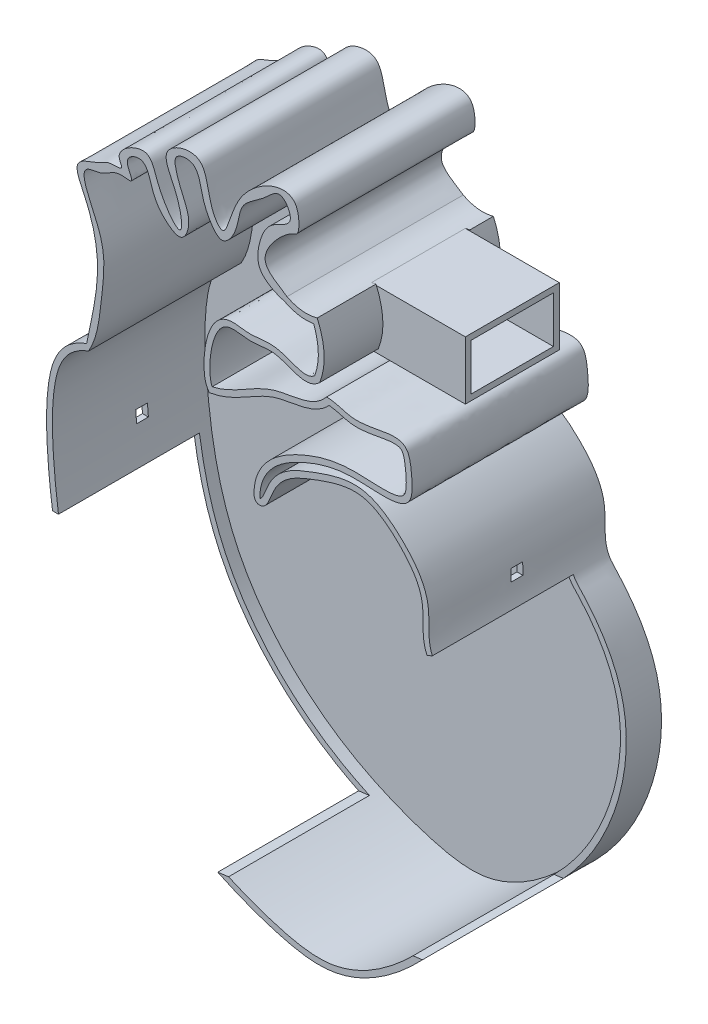
SolidWorks part; units mm, degrees
ref_plane "Front Plane" through (0, 0, 0) normal (0, 0, 1) x (1, 0, 0)
ref_plane "Top Plane" through (0, 0, 0) normal (0, 1, 0) x (1, 0, 0)
ref_plane "Right Plane" through (0, 0, 0) normal (1, 0, 0) x (0, 0, -1)
sketch "Sketch1" plane through (0, 0, 0) normal (0, 0, 1) x (1, 0, 0)
  line L0 (155.9186, 311.1659) -> (244.8186, 311.1659) construction
  line L1 (156.5316, 303.0783) -> (161.4308, 303.0783) construction
  line L2 (233.7391, 314.6833) -> (238.69, 317.0002) construction
  spline S0 degree 3 poles (163.9083, 338.1039) (161.9768, 337.4412) (157.1029, 334.2543) (154.9102, 324.3198) (155.5747, 306.9623) (159.3352, 282.8965) (178.2163, 259.8183) (198.5453, 249.6184) (218.658, 245.0232) (234.9705, 255.6289) (248.3574, 273.7717) (252.562, 297.43) (244.0287, 311.0697) (237.1441, 318.0888) (239.2563, 326.9522) (232.8796, 335.434) (223.6557, 342.294) (212.2823, 338.3975) (203.9965, 334.9615) (202.0734, 328.1414) (201.373, 327.7878) knots 0 0 0 0 0.018356 0.050113 0.089989 0.184834 0.273022 0.359649 0.397817 0.461195 0.526427 0.612455 0.666069 0.672634 0.70355 0.738354 0.768396 0.804572 0.842171 0.854276 0.854276 0.854276 0.854276
  spline S1 degree 3 poles (201.373, 327.7878) (201.2411, 334.1721) (210.0961, 339.7603) (221.5494, 342.7293) (234.6091, 340.3552) (234.3082, 348.414) (233.1347, 356.5821) (224.4197, 351.8287) (218.6092, 353.6578) (216.1039, 354.182) (215.7479, 353.9628) (215.7115, 353.9491) knots 0 0 0 0 0.06497 0.106572 0.152532 0.172856 0.189447 0.237486 0.244272 0.257313 0.258771 0.258771 0.258771 0.258771
  spline S2 degree 3 poles (191.0565, 343.5913) (189.9532, 345.5895) (190.6329, 358.3632) (199.3878, 355.7857) (206.0148, 357.7805) (211.1953, 353.0561) (214.3082, 355.9865) knots 0 0 0 0 0.405824 0.53697 0.698075 1 1 1 1
  spline S3 degree 2 poles (214.3082, 355.9865) (216.501, 361.6168) (213.771, 367.8191) knots 0 0 0 1 1 1
  spline S4 degree 3 poles (207.2459, 368.5487) (205.0598, 370.021) (199.5317, 372.8057) (208.0158, 381.653) (209.9817, 380.8555) (209.6995, 391.1997) (195.4946, 384.7438) (194.2273, 371.497) (189.9441, 377.9485) (190.0533, 387.2336) (178.7068, 383.43) (183.9867, 376.0122) (185.3676, 366.1697) (178.9279, 374.9689) (177.7722, 382.4586) (169.3528, 377.5588) (172.5077, 374.2031) (168.697, 374.7265) (166.012, 372.7624) (160.2072, 371.6213) (168.517, 356.8615) (166.0282, 348.5222) (163.9083, 338.1039) knots 0.32525 0.32525 0.32525 0.32525 0.35533 0.400071 0.424306 0.445546 0.499592 0.537543 0.556665 0.593447 0.628022 0.659336 0.693837 0.728583 0.755387 0.783229 0.795802 0.810719 0.82063 0.845086 0.871446 1 1 1 1
  spline S5 degree 3 poles (191.0565, 343.5913) (195.8739, 344.5751) (203.0191, 351.2998) (212.7468, 350.3373) (215.7115, 353.9491) knots 0 0 0 0 0.545988 1 1 1 1
  spline S6 degree 2 poles (207.2459, 368.5487) (210.4279, 366.9183) (213.771, 367.8191) knots 0 0 0 1 1 1
  spline S7 degree 2 poles (214.3082, 355.9865) (214.1778, 355.871) (214.0493, 355.757) knots 0 0 0 0.004863 0.004863 0.004863
  spline S8 degree 1 poles (190.3959, 342.1602) (213.4377, 356.9113) knots 0 0 1 1 construction
  spline S9 degree 1 poles (190.3959, 342.1602) (216.3571, 352.7546) knots 0 0 1 1 construction
  spline S10 degree 1 poles (200.1033, 327.7616) (216.3571, 352.7546) knots 0 0 1 1 construction
  spline S11 degree 3 poles (213.4377, 356.9113) (213.3137, 356.7945) (213.0377, 356.5641) (212.5489, 356.2586) (211.9624, 356.0434) (211.2208, 355.978) (210.0832, 356.1171) (208.4017, 356.6868) (206.5023, 357.422) (204.8117, 357.8171) (203.0545, 357.9215) (201.5009, 357.7248) (200.0481, 357.5829) (199.0364, 357.555) (197.9699, 357.6667) (196.758, 357.8356) (195.4825, 357.9343) (194.0723, 357.7749) (192.7564, 357.1034) (191.7635, 356.1272) (190.9912, 354.9559) (190.2, 353.2117) (189.5644, 350.792) (189.2946, 348.3345) (189.2678, 346.5233) (189.3384, 345.2819) (189.471, 344.3745) (189.635, 343.7199) (189.7643, 343.3459) (189.893, 343.0709) (189.9627, 342.9448) (190.0014, 342.8746) (190.0604, 342.7678) (190.1933, 342.5272) (190.3062, 342.3225) (190.3959, 342.1602) knots -0.055328 -0.055328 -0.055328 -0.055328 -0.038839 -0.022349 0.01063 0.043609 0.076588 0.142546 0.208504 0.241483 0.274462 0.34042 0.373399 0.406378 0.439357 0.472336 0.505315 0.538294 0.571273 0.604252 0.637231 0.67021 0.736168 0.802126 0.835105 0.868084 0.901063 0.917552 0.934042 0.942287 0.946409 0.950531 0.958776 0.967021 1 1 1 1
  spline S12 degree 3 poles (190.3959, 342.1602) (190.6771, 342.2176) (191.2188, 342.3238) (192.4678, 342.6053) (194.4928, 343.2888) (197.1927, 344.625) (200.2083, 346.3831) (202.6688, 347.657) (204.6346, 348.3885) (206.6793, 348.8914) (208.9604, 349.2245) (211.3111, 349.7503) (213.0805, 350.3563) (214.518, 351.1414) (215.5965, 351.981) (216.1163, 352.4904) (216.3571, 352.7546) knots -0.034555 -0.034555 -0.034555 -0.034555 -0.002686 0.029184 0.092922 0.2204 0.347877 0.475355 0.539094 0.602833 0.73031 0.794049 0.857788 0.921526 0.953396 0.985265 0.985265 0.985265 0.985265
  spline S13 degree 3 poles (216.3571, 352.7546) (216.4193, 352.7488) (216.5354, 352.7354) (216.8314, 352.6923) (217.4199, 352.5845) (218.4001, 352.3577) (219.468, 352.0501) (220.6435, 351.7445) (221.937, 351.6179) (223.6212, 351.6531) (225.7051, 351.9464) (228.0442, 352.4022) (229.7329, 352.6434) (230.7985, 352.6461) (231.4108, 352.5491) (231.8114, 352.3765) (232.0592, 352.1749) (232.3128, 351.7789) (232.6496, 350.8086) (232.8957, 349.0663) (233.0494, 347.1696) (233.0362, 345.8716) (232.9384, 345.0375) (232.7503, 344.4014) (232.5216, 344.0145) (232.1958, 343.698) (231.5494, 343.3217) (230.2865, 342.9886) (227.5594, 342.8378) (224.2529, 343.077) (221.0286, 343.1111) (218.0533, 342.8829) (214.6591, 342.1734) (210.8661, 340.7717) (206.9559, 338.8813) (203.9901, 336.6944) (202.072, 334.4577) (200.9476, 332.5101) (200.3521, 330.6519) (200.1221, 329.0464) (200.0946, 328.1851) (200.1033, 327.7616) knots 0 0 0 0 0.00099 0.00198 0.00396 0.007921 0.011881 0.015841 0.019801 0.023762 0.031682 0.039603 0.047523 0.051484 0.055444 0.059404 0.063364 0.067325 0.071285 0.079205 0.087126 0.091086 0.095046 0.099007 0.102967 0.106927 0.110888 0.118808 0.126729 0.14257 0.15049 0.158411 0.174252 0.190093 0.205934 0.221775 0.229696 0.237616 0.245537 0.249497 0.253457 0.253457 0.253457 0.253457
  spline S14 degree 1 poles (213.1248, 356.4474) (212.998, 366.3558) knots 0 0 1 1 construction
  spline S15 degree 1 poles (206.6668, 367.4184) (212.998, 366.3558) knots 0 0 1 1 construction
  spline S16 degree 2 poles (213.1248, 356.4474) (213.814, 358.2195) (214.073, 361.2517) (213.7436, 364.3754) (212.998, 366.3558) knots 0 0 0 0.344218 0.573697 0.917916 0.917916 0.917916
  spline S17 degree 2 poles (212.998, 366.3558) (209.7287, 365.8442) (206.6668, 367.4184) knots 0 0 0 0.853875 0.853875 0.853875
  spline S18 degree 1 poles (164.3204, 336.9026) (201.9454, 326.6541) knots 0 0 1 1 construction
  spline S19 degree 3 poles (164.3204, 336.9026) (163.074, 336.475) (160.654, 335.1123) (158.3654, 332.1538) (157.1447, 328.3475) (156.6088, 324.1226) (156.4342, 319.9796) (156.5503, 315.8432) (156.8409, 311.6653) (157.3603, 306.061) (158.3559, 299.0807) (160.3211, 290.9132) (163.2799, 283.148) (167.4499, 275.9058) (172.6452, 269.2842) (178.6842, 263.4134) (185.3663, 258.4307) (192.6113, 254.3241) (199.0594, 251.6013) (204.4485, 249.8179) (208.5491, 248.6969) (212.6004, 248.0494) (216.4983, 248.1033) (220.3196, 249.0202) (225.3152, 251.19) (230.0324, 254.5252) (234.2544, 258.3893) (238.0784, 262.4583) (242.1279, 267.9905) (245.8565, 275.4597) (248.3547, 283.6918) (249.0642, 290.7081) (248.6419, 296.1774) (247.7889, 300.1393) (246.3596, 303.9413) (244.7446, 306.9659) (243.2323, 309.2802) (241.9964, 310.9603) (240.8905, 312.3075) (239.9618, 313.3579) (239.2518, 314.1151) (238.4639, 314.9566) (237.7244, 316.0083) (237.2329, 317.1348) (236.8209, 318.6721) (236.6514, 320.6098) (236.6609, 322.8813) (236.6302, 325.0243) (236.225, 327.5214) (234.8799, 330.4352) (232.2611, 333.637) (229.0675, 336.6162) (225.6696, 338.8) (222.2516, 339.59) (218.3647, 339.0472) (214.941, 337.9064) (212.1889, 336.875) (210.2507, 336.0908) (208.4841, 335.1952) (206.9257, 334.123) (205.5893, 332.7897) (204.659, 331.3872) (204.0361, 329.9842) (203.6426, 328.9825) (203.2952, 328.2157) (202.996, 327.6632) (202.6721, 327.2167) (202.3157, 326.8779) (202.0703, 326.7171) (201.9454, 326.6541) knots 0 0 0 0 0.013348 0.026696 0.040044 0.053392 0.06674 0.080088 0.093436 0.106785 0.133481 0.160177 0.186873 0.213569 0.240265 0.266961 0.293657 0.320354 0.34705 0.360398 0.373746 0.387094 0.400442 0.41379 0.427138 0.453834 0.467182 0.48053 0.507226 0.533923 0.560619 0.587315 0.600663 0.614011 0.627359 0.640707 0.647381 0.654055 0.660729 0.664066 0.667403 0.67074 0.674077 0.677414 0.680751 0.687425 0.694099 0.700773 0.707447 0.720795 0.734144 0.747492 0.76084 0.774188 0.787536 0.800884 0.807558 0.814232 0.820906 0.82758 0.834254 0.840928 0.844265 0.847602 0.849271 0.850939 0.852608 0.853442 0.854276 0.854276 0.854276 0.854276
  spline S20 degree 2 poles (200.1033, 327.7616) (200.4305, 326.1535) (201.9454, 326.6541) knots 0 0 0 1 1 1
  spline S21 degree 3 poles (164.3204, 336.9026) (166.2448, 340.2411) (166.8696, 346.4619) (168.0792, 355.6471) (166.3225, 362.3306) (161.4238, 371.1385) (167.8741, 371.3025) (169.8559, 373.9915) (174.9082, 372.7609) (171.1679, 377.1128) (176.6117, 379.5656) (178.025, 373.5994) (179.9383, 370.176) (184.5394, 367.1645) (186.6466, 371.7902) (184.8999, 375.8424) (183.3682, 379.313) (182.6201, 383.3592) (187.7283, 384.1124) (188.6956, 378.9298) (189.7932, 375.3548) (193.1125, 370.7349) (196.8953, 375.6145) (196.6258, 381.3794) (201.8868, 383.6842) (205.9003, 388.4535) (209.4253, 382.3511) (203.3413, 380.8803) (201.1851, 376.2932) (200.3437, 369.9393) (204.8247, 367.9128) (206.6668, 367.4184) knots 0 0 0 0 0.076999 0.134833 0.184407 0.243566 0.261661 0.297591 0.312369 0.336081 0.35936 0.389532 0.433792 0.456295 0.478515 0.514098 0.547063 0.563355 0.587317 0.618087 0.65289 0.679695 0.706127 0.74904 0.794105 0.821074 0.850118 0.880461 0.920008 0.954846 1 1 1 1
  dimension "D1" = 88.9
extrude "Boss-Extrude1" add sketch "Sketch1" along normal blind 5.08 contours S3 S6 S4 S0 S1 S5 S2
extrude "Boss-Extrude2" add sketch "Sketch1<6>" along normal blind 38.1 contours S7 S3 S6 S4 S0 S1 S5 S2 S19 S21 S17 S16 S11 S12 S13 S20 region at (200.712, 331.6182, 0)
sketch "Sketch1<6>" plane through (0, 0, 0) normal (0, 0, 1) x (1, 0, 0) same geometry as "Sketch1"
ref_plane "Plane1" through (0, 0, 7.62) normal (0, 0, 1) x (1, 0, 0)
sketch "Sketch3" plane through (0, 0, 7.62) normal (0, 0, 1) x (1, 0, 0)
  line L0 (154.3986, 303.0783) -> (165.0584, 303.0783)
  line L1 (165.0584, 303.0783) -> (226.4735, 313.7797)
  line L2 (226.4735, 313.7797) -> (233.7391, 314.6833)
  line L3 (233.7391, 314.6833) -> (238.69, 317.0002)
  line L4 (238.69, 317.0002) -> (245.8362, 320.3446)
  line L5 (245.8362, 320.3446) -> (268.8706, 294.1559)
  line L6 (268.8706, 294.1559) -> (260.2472, 270.9364)
  line L7 (260.2472, 270.9364) -> (242.9423, 259.8155)
  line L8 (242.9423, 259.8155) -> (190.258, 253.0022)
  line L9 (190.258, 253.0022) -> (163.5423, 255.7374)
  line L10 (163.5423, 255.7374) -> (142.1916, 294.1559)
  line L11 (142.1916, 294.1559) -> (154.3986, 303.0783)
extrude "Cut-Extrude1" cut sketch "Sketch3" along normal blind 38.1
sketch "Sketch4" plane through (0, 0, 7.62) normal (0, 0, 1) x (1, 0, 0)
  line L0 (230.2336, 352.3104) -> (235.9323, 352.8119)
  line L1 (235.9323, 352.8119) -> (236.6859, 344.2473)
  line L2 (236.6859, 344.2473) -> (230.2336, 344.2473)
  line L3 (230.2336, 344.2473) -> (230.2336, 352.3104)
  line L7 (217.6315, 357.1847) -> (214.9144, 356.2061)
  line L8 (214.9144, 356.2061) -> (212.1857, 356.6954)
  line L10 (205.0851, 386.0122) -> (206.4718, 387.0869)
  line L11 (206.4718, 387.0869) -> (209.5516, 386.6965)
  line L12 (209.5516, 386.6965) -> (211.8364, 385.2149)
  line L13 (211.8364, 385.2149) -> (211.8364, 382.3722)
  line L14 (211.8364, 382.3722) -> (207.1339, 382.9683)
  line L15 (207.1339, 382.9683) -> (205.0851, 386.0122)
  line L16 (181.0651, 384.4902) -> (183.9348, 381.6205)
  line L17 (183.9348, 381.6205) -> (186.1585, 382.3722)
  line L18 (186.1585, 382.3722) -> (186.6359, 382.8496)
  line L19 (186.6359, 382.8496) -> (185.9775, 386.0122)
  line L20 (185.9775, 386.0122) -> (181.0651, 384.4902)
  line L21 (170.4015, 378.9548) -> (173.3307, 376.0256)
  line L22 (173.3307, 376.0256) -> (175.1018, 377.2176)
  line L23 (175.1018, 377.2176) -> (176.0846, 377.2176)
  line L24 (176.0846, 377.2176) -> (175.2313, 381.3161)
  line L25 (175.2313, 381.3161) -> (170.4015, 378.9548)
  line L26 (162.0611, 372.1241) -> (164.1929, 369.4765)
  line L27 (164.1929, 369.4765) -> (168.2352, 370.7288)
  line L28 (168.2352, 370.7288) -> (171.8661, 371.4848)
  line L29 (171.8661, 371.4848) -> (169.3576, 375.8171)
  line L30 (169.3576, 375.8171) -> (164.1929, 374.0713)
  line L31 (164.1929, 374.0713) -> (162.0611, 372.1241)
  line L33 (218.5137, 354.5651) -> (212.0445, 354.5651)
  line L34 (218.5137, 354.5651) -> (218.5137, 368.4837)
  line L35 (218.5137, 368.4837) -> (212.0445, 368.4837)
  line L36 (212.0445, 354.5651) -> (212.0445, 368.4837)
  line L37 (218.5137, 354.5651) -> (212.0445, 368.4837) construction
  line L38 (218.5137, 368.4837) -> (212.0445, 354.5651) construction
  parabola Q0 (214.3082, 355.9865) -> (213.771, 367.8191) focus (208.3433, 360.3094) apex (215.1925, 359.5136) construction
  point P2 (215.2791, 361.5244)
ref_plane "Plane2" through (160.02, 0, 0) normal (1, 0, 0) x (0, 0, -1)
sketch "Sketch5" plane through (160.02, 0, 0) normal (1, 0, 0) x (0, 0, -1)
  line L0 (-38.1, 303.0783) -> (-10.0634, 303.0783) construction
  line L1 (-38.1, 303.0783) -> (-7.62, 303.0783) construction
  line L2 (-38.1, 336.9026) -> (-38.1, 303.0783) construction
  line L3 (-17.78, 310.6983) -> (-20.32, 310.6983)
  line L4 (-17.78, 310.6983) -> (-17.78, 313.2383)
  line L5 (-17.78, 313.2383) -> (-20.32, 313.2383)
  line L6 (-20.32, 310.6983) -> (-20.32, 313.2383)
  line L7 (-17.78, 310.6983) -> (-20.32, 313.2383) construction
  line L8 (-17.78, 313.2383) -> (-20.32, 310.6983) construction
  line L9 (-38.1, 314.557) -> (-38.1, 303.0783) construction
  point P5 (-19.05, 311.9683)
  dimension "D1" = 2.54
  dimension "D2" = 2.54
  dimension "D3" = 19.05
  dimension "D4" = 7.62
ref_plane "Plane3" through (231.14, 0, 0) normal (1, 0, 0) x (0, 0, -1)
sketch "Sketch6" plane through (231.14, 0, 0) normal (1, 0, 0) x (0, 0, -1)
  line L0 (-38.1, 316.4615) -> (-7.62, 316.4615) construction
  line L1 (-38.1, 316.4615) -> (-38.1, 326.3249) construction
  line L2 (-38.1, 340.6426) -> (-38.1, 317.0002) construction
  line L4 (-17.78, 321.5415) -> (-20.32, 321.5415)
  line L5 (-17.78, 321.5415) -> (-17.78, 324.0815)
  line L6 (-17.78, 324.0815) -> (-20.32, 324.0815)
  line L7 (-20.32, 321.5415) -> (-20.32, 324.0815)
  line L8 (-17.78, 321.5415) -> (-20.32, 324.0815) construction
  line L9 (-17.78, 324.0815) -> (-20.32, 321.5415) construction
  point P4 (-19.05, 322.8115)
  dimension "D1" = 2.54
  dimension "D2" = 2.54
  dimension "D3" = 19.05
  dimension "D4" = 5.08
extrude "Cut-Extrude3" cut sketch "Sketch6" along normal blind 38.1
extrude "Cut-Extrude4" cut sketch "Sketch5" against normal blind 38.1
ref_plane "Plane5" through (213.36, 0, 0) normal (1, 0, 0) x (0, 0, -1)
sketch "Sketch8" plane through (0, 0, 5.08) normal (0, 0, 1) x (1, 0, 0)
  line L1 (224.2581, 354.8006) -> (212.7953, 354.8006)
  line L2 (224.2581, 354.8006) -> (224.2581, 369.2281)
  line L3 (224.2581, 369.2281) -> (212.7953, 369.2281)
  line L4 (212.7953, 354.8006) -> (212.7953, 369.2281)
  line L5 (224.2581, 354.8006) -> (212.7953, 369.2281) construction
  line L6 (224.2581, 369.2281) -> (212.7953, 354.8006) construction
  point P0 (218.5267, 362.0144)
extrude "Cut-Extrude5" cut sketch "Sketch8" along normal blind 20.32
sketch "Sketch9" plane through (212.7953, 0, 0) normal (1, 0, 0) x (0, 0, -1)
  line L0 (-24.13, 366.3395) -> (-24.13, 356.2762)
  line L1 (-25.4, 367.6095) -> (-5.08, 367.6095)
  line L2 (-25.4, 367.6095) -> (-25.4, 355.0062)
  line L3 (-25.4, 355.0062) -> (-5.08, 355.0062)
  line L4 (-5.08, 367.6095) -> (-5.08, 355.0062)
  line L5 (-24.13, 356.2762) -> (-6.35, 356.2762)
  line L6 (-6.35, 366.3395) -> (-6.35, 356.2762)
  line L7 (-24.13, 366.3395) -> (-6.35, 366.3395)
  dimension "D1" = 1.27
extrude "Boss-Extrude4" add sketch "Sketch9" along normal blind 20.32
